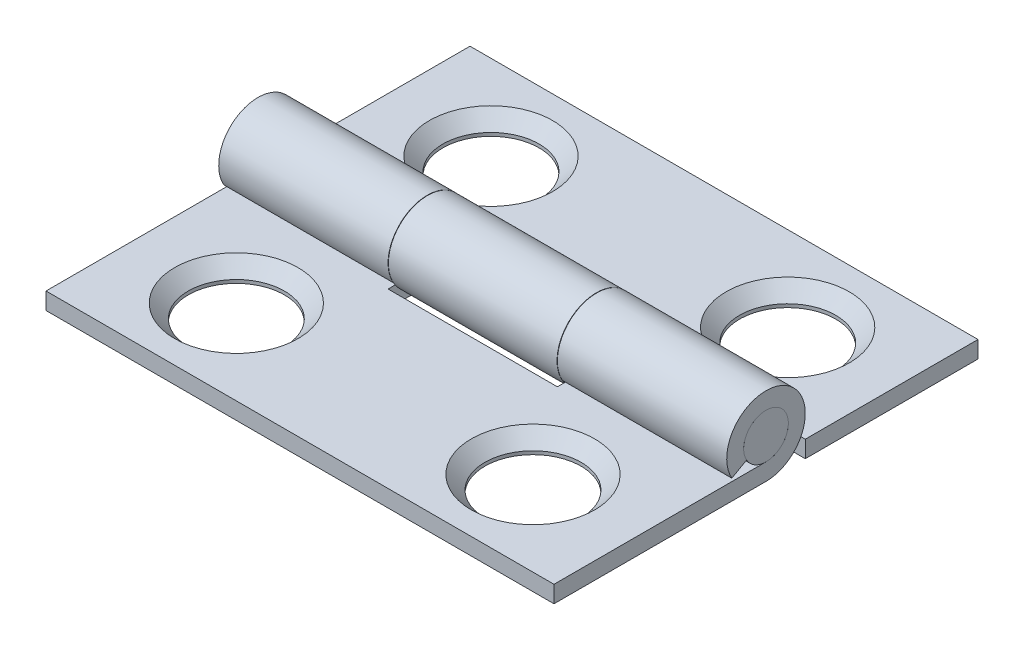
SolidWorks part; units mm, degrees
ref_plane "Front Plane" through (0, 0, 0) normal (0, 0, 1) x (1, 0, 0)
ref_plane "Top Plane" through (0, 0, 0) normal (0, 1, 0) x (1, 0, 0)
ref_plane "Right Plane" through (0, 0, 0) normal (1, 0, 0) x (0, 0, -1)
sketch "Sketch1" plane through (0, 0, 0) normal (0, 1, 0) x (1, 0, 0)
  line L0 (-9.525, 0) -> (9.525, 0) construction
  line L1 (-9.525, -7.9502) -> (-9.525, 7.9502) construction
  line L2 (-9.525, -7.9502) -> (-5.5626, -7.9502) construction
  line L3 (5.5626, -4.7752) -> (-5.5626, -4.7752) construction
  line L4 (-5.5626, -7.9502) -> (5.5626, -7.9502) construction
  line L5 (9.525, -7.9502) -> (9.525, -4.7752) construction
  line L6 (5.5626, -7.9502) -> (9.525, -7.9502) construction
  line L7 (-9.525, 7.9502) -> (-4.7498, 7.9502) construction
  line L8 (-4.7498, 7.9502) -> (11.1252, 7.9502) construction
  line L9 (11.1252, 7.9502) -> (27.0002, 7.9502) construction
  line L10 (27.0002, 7.9502) -> (30.9626, 7.9502) construction
  line L11 (5.5626, -7.0866) -> (5.5626, -2.4638) construction
  line L12 (5.5626, -4.7752) -> (9.525, -4.7752) construction
  line L13 (-5.5626, -4.7752) -> (-5.5626, -7.9502) construction
  line L14 (5.5626, 4.7752) -> (-5.5626, 4.7752) construction
  point P3 (5.5626, -6.5786)
  point P4 (0, 0)
  point P8 (-9.525, 0)
  point P17 (-3.175, 0)
  point P21 (5.5626, -4.7752)
  dimension "Frame Leaf Height" = 19.05
  dimension "Overall Width" = 15.9004
  dimension "Hole to End 1" = 3.9624
  dimension "Hole to End 2" = 3.9624
  dimension "D1" = 3.9624
  dimension "D2" = 4.7752
  dimension "D4" = 15.875
  dimension "D6" = 15.875
  dimension "Knuckle Length" = 6.35
  dimension "Hole Chamfer Dia" = 4.6228
  dimension "Hole Center to Pin" = 4.7752
  dimension "Door Leaf Height" = 19.05
  dimension "Mounting Hole Diameter" = 3.6068
  dimension "D3" = 11.1252
  dimension "Frame Leaf Width" = 7.9502
  dimension "Door Leaf Width" = 7.9502
sketch "Sketch2" plane through (0, 0, 0) normal (1, 0, 0) x (0, 0, -1)
  line L2 (0, -1.4732) -> (0, -0.8382) construction
  line L4 (0, 0.8382) -> (0, -0.8382) construction
  point P8 (0, 0)
  dimension "Leaf Thickness" = 0.635
  dimension "Pin Diameter" = 1.6764
sketch "Sketch3" plane through (0, 0, 0) normal (1, 0, 0) x (0, 0, -1)
  line L3 (0, 0) -> (-1.4732, -0.8382) construction
  line L4 (0, -1.4732) -> (-7.9502, -1.4732)
  line L5 (-7.9502, -1.4732) -> (-7.9502, -0.8382)
  line L7 (-7.9502, -0.8382) -> (0, -0.8382)
  line L8 (-7.9502, 0) -> (7.9502, 0) construction
  line L9 (-0.7285, -0.4145) -> (-1.2805, -0.7285)
  line L11 (-1.4732, 0) -> (-1.4732, -0.8382) construction
  circle A4 centre (0, 0) radius 0.8382 construction
  circle A5 centre (0, 0) radius 1.4732 construction
  arc A8 (-0.7285, -0.4145) -> (0, -0.8382) centre (0, 0) cw
  arc A9 (-1.2805, -0.7285) -> (0, -1.4732) centre (0, 0) cw
  point P0 (-1.2805, -0.7285)
  point P13 (-0.7285, -0.4145)
extrude "Boss-Extrude1" add sketch "Sketch3" along normal mid plane 19.05
pattern_circular "CirPattern1" count 2 over 360 about axis through (0, 0.8382, 0) along (0, -1, 0) reverse direction yes of bodies 104 107
sketch "Sketch4" plane through (0, 0, 0) normal (0, 1, 0) x (1, 0, 0)
  line L0 (-9.525, -1.4732) -> (9.525, -1.4732) construction
  line L1 (-9.525, -1.4732) -> (9.525, -1.4732) construction
  line L2 (9.525, 1.4732) -> (-9.525, 1.4732) construction
  line L3 (9.525, 1.4732) -> (-9.525, 1.4732) construction
  line L4 (-3.175, -1.4732) -> (-3.175, 1.4732)
  line L6 (-3.175, 1.4732) -> (3.175, 1.4732)
  line L7 (3.175, -1.4732) -> (-3.175, -1.4732)
  line L8 (3.175, 1.4732) -> (3.175, -1.4732)
  point P8 (-3.175, 0)
  dimension "D1" = 6.35
extrude "Cut-Extrude1" cut sketch "Sketch4" against normal through all both and the other way through all
sketch "Sketch10" plane through (0, 0, 0) normal (0, 1, 0) x (1, 0, 0)
  line L0 (9.525, 1.4732) -> (-9.525, 1.4732) construction
  line L5 (-3.1623, 1.4732) -> (-9.525, 1.4732)
  line L6 (-3.1623, 1.4732) -> (-3.1623, -1.4732)
  line L7 (-3.1623, -1.4732) -> (-9.525, -1.4732)
  line L8 (-9.525, 1.4732) -> (-9.525, -1.4732)
  line L9 (3.1623, 1.4732) -> (9.525, 1.4732)
  line L10 (3.1623, 1.4732) -> (3.1623, -1.4732)
  line L11 (3.1623, -1.4732) -> (9.525, -1.4732)
  line L12 (9.525, 1.4732) -> (9.525, -1.4732)
  dimension "D1" = 0.0127
extrude "Cut-Extrude4" cut sketch "Sketch10" against normal through all both and the other way through all
sketch "Sketch5" plane through (0, -0.8382, 0) normal (0, 1, 0) x (1, 0, 0)
  line L0 (5.5626, -4.7752) -> (-5.5626, -4.7752) construction
  line L1 (0, -4.7752) -> (0, -7.9502) construction
  line L2 (-5.5626, -4.7752) -> (-5.5626, -7.9502) construction
  line L3 (9.525, -7.9502) -> (-9.525, -7.9502) construction
  circle A0 centre (5.5626, -4.7752) radius 2.3114
  circle A2 centre (-5.5626, -4.7752) radius 2.3114
extrude "Cut-Extrude2" cut sketch "Sketch5" against normal through all draft 45
sketch "Sketch9" plane through (0, 0, 0) normal (0, 1, 0) x (1, 0, 0)
  circle A0 centre (5.5626, -4.7752) radius 1.8034
  circle A2 centre (-5.5626, -4.7752) radius 1.8034
  dimension "D1" = 3.6068
extrude "Cut-Extrude3" cut sketch "Sketch9" against normal through all both and the other way through all
sketch "Sketch11" plane through (0, -0.8382, 0) normal (0, 1, 0) x (1, 0, 0)
  circle A0 centre (5.5626, 4.7752) radius 2.3114
  circle A1 centre (-5.5626, 4.7752) radius 2.3114
  circle A2 centre (-5.5626, -4.7752) radius 2.3114 construction
extrude "Cut-Extrude5" cut sketch "Sketch11" against normal through all draft 45
sketch "Sketch12" plane through (0, -0.8382, 0) normal (0, 1, 0) x (1, 0, 0)
  circle A0 centre (-5.5626, 4.7752) radius 1.8034
  circle A1 centre (5.5626, 4.7752) radius 1.8034
  circle A2 centre (-5.5626, -4.7752) radius 1.8034 construction
extrude "Cut-Extrude6" cut sketch "Sketch12" against normal through all both and the other way through all
sketch "Sketch6" plane through (0, 0, 0) normal (1, 0, 0) x (0, 0, -1)
  circle A0 centre (0, 0) radius 0.8382
  dimension "D1" = 1.6764
extrude "Boss-Extrude2" add sketch "Sketch6" along normal mid plane 19.05 separate body
sketch "Sketch7" plane through (0, 0, 0) normal (1, 0, 0) x (0, 0, -1)
  line L0 (-0.8382, 0) -> (0.8382, 0) construction
  line L1 (-7.9502, 0) -> (7.9502, 0) construction
  line L2 (7.9502, -0.8382) -> (7.9502, -1.4732) construction
  line L3 (7.9502, -0.8382) -> (7.9502, -1.4732) construction
  line L4 (7.9502, -1.4732) -> (-7.9502, -1.4732) construction
  line L5 (-7.9502, -1.4732) -> (-7.9502, -0.8382)
  point P6 (0, 0)
  point P8 (0.8382, 0)
  point P9 (-0.8382, 0)
  point P12 (7.9502, -0.8382)
  point P13 (7.9502, -1.4732)
  point P14 (-7.9502, -1.4732)
  dimension "D1" = 1.6764
  dimension "D2" = 15.9004
  dimension "D3" = 0.635
sketch "Sketch8" plane through (0, 0, 0) normal (0, 1, 0) x (1, 0, 0)
  line L0 (-7.874, -4.7752) -> (-3.2512, -4.7752) construction
  line L1 (5.5626, 4.7752) -> (-5.5626, 4.7752) construction
  line L2 (3.2512, -4.7752) -> (7.874, -4.7752) construction
  line L3 (-5.5626, -2.4638) -> (-5.5626, -7.0866) construction
  line L5 (5.5626, -2.4638) -> (5.5626, -7.0866) construction
  line L6 (-5.5626, 7.0866) -> (-5.5626, 2.4638) construction
  line L7 (-7.874, 4.7752) -> (-3.2512, 4.7752) construction
  line L10 (5.5626, 7.0866) -> (5.5626, 2.4638) construction
  line L11 (3.2512, 4.7752) -> (7.874, 4.7752) construction
  line L12 (5.5626, 4.7752) -> (7.197, 6.4096) construction
  circle A1 centre (-5.5626, -4.7752) radius 2.3114 construction
  circle A3 centre (5.5626, -4.7752) radius 2.3114 construction
  circle A7 centre (5.5626, 4.7752) radius 2.3114 construction
  circle A8 centre (-5.5626, 4.7752) radius 2.3114 construction
  circle A9 centre (5.5626, 4.7752) radius 2.3114 construction
  point P2 (-9.525, 0)
  point P7 (-5.5626, -4.7752)
  point P19 (5.5626, -4.7752)
  point P25 (-9.525, 7.9502)
  point P26 (30.9626, 7.9502)
  point P28 (-9.525, -7.9502)
  point P30 (9.525, -7.9502)
  point P32 (-7.874, -4.7752)
  point P33 (-5.5626, -2.4638)
  point P34 (-3.2512, -4.7752)
  point P35 (-5.5626, -7.0866)
  point P40 (7.874, -4.7752)
  point P41 (5.5626, -7.0866)
  point P42 (3.2512, -4.7752)
  point P43 (5.5626, -2.4638)
  point P67 (5.5626, -7.9502)
  point P69 (-5.5626, -7.9502)
  point P71 (-4.7498, 7.9502)
  point P73 (-5.5626, 4.7752)
  point P76 (5.5626, 4.7752)
  point P77 (27.0002, 7.9502)
  point P78 (11.1252, 7.9502)
  point P82 (-5.5626, 7.0866)
  point P83 (-7.874, 4.7752)
  point P84 (-5.5626, 2.4638)
  point P85 (-3.2512, 4.7752)
  point P90 (5.5626, 2.4638)
  point P91 (3.2512, 4.7752)
  point P92 (5.5626, 7.0866)
  point P97 (7.197, 6.4096)
  dimension "D1" = 45
equation "\"D1@Sketch1\"=\"Hole to End 1@Sketch1\""
equation "\"D6@Sketch1\"=\"D4@Sketch1\""
equation "\"D1@Boss-Extrude1\" = \"Frame Leaf Height@Sketch1\""
equation "\"D1@Sketch4\"=\"Knuckle Length@Sketch1\""
equation "\"D1@Sketch6\"=\"Pin Diameter@Sketch2\""
equation "\"D1@Boss-Extrude2\" = \"Frame Leaf Height@Sketch1\""
equation "\"D1@Sketch7\"=\"Pin Diameter@Sketch2\""
equation "\"D2@Sketch7\"=\"Overall Width@Sketch1\""
equation "\"D3@Sketch7\"=\"Leaf Thickness@Sketch2\""
equation "\"Knuckle Length@Sketch1\"=\"Frame Leaf Height@Sketch1\" / 3"
equation "\"Hole to End 2@Sketch1\"=\"Hole to End 1@Sketch1\""
equation "\"D1@Sketch9\"=\"Mounting Hole Diameter@Sketch1\""
equation "\"Hole Chamfer Dia@Sketch1\"=\"Mounting Hole Diameter@Sketch1\"+.04"
